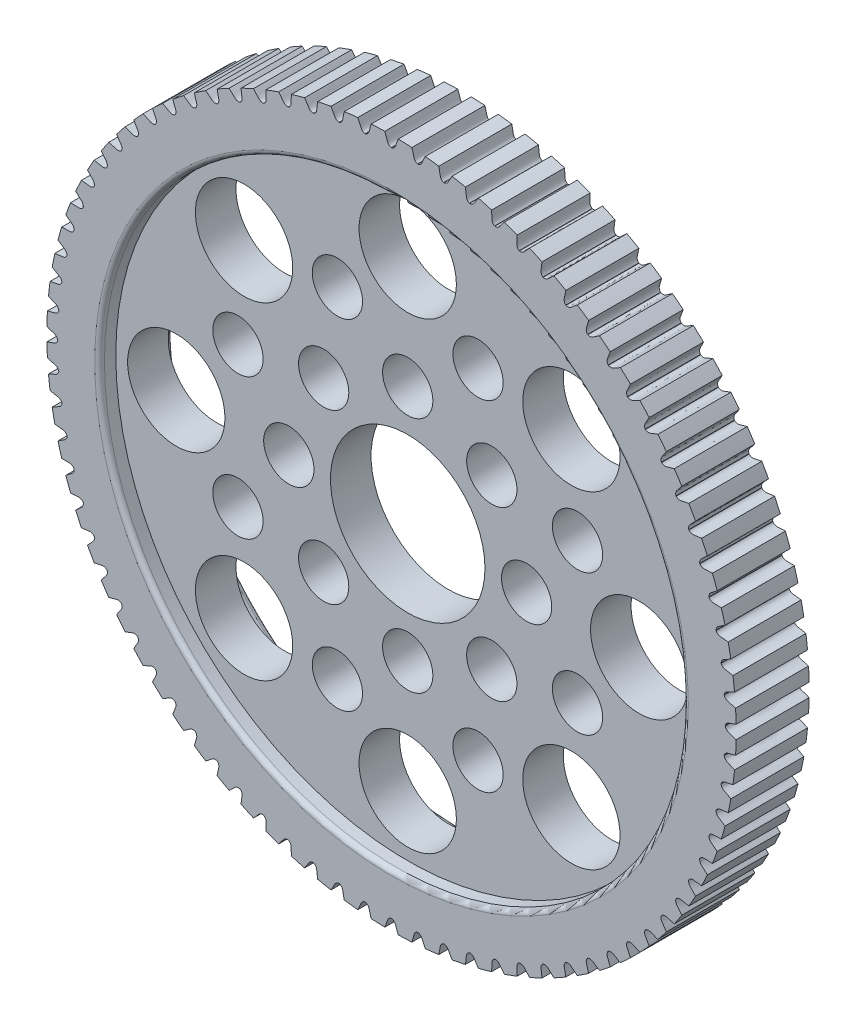
SolidWorks part; units mm, degrees
material "铝合金板 LF5"
ref_plane "前视基准面" through (0, 0, 0) normal (0, 0, 1) x (1, 0, 0)
ref_plane "上视基准面" through (0, 0, 0) normal (0, 1, 0) x (1, 0, 0)
ref_plane "右视基准面" through (0, 0, 0) normal (1, 0, 0) x (0, 0, -1)
sketch "草图1" plane through (0, 0, 0) normal (0, 0, 1) x (1, 0, 0)
  circle A0 centre (0, 0) radius 21.25
  dimension "D1" = 42.5
extrude "凸台-拉伸1" add sketch "草图1" along normal blind 4.5
ref_axis "基准轴1" through (0, 0, 4.5) along (0, 0, -1)
sketch "草图2" plane through (0, 0, 0) normal (0, 0, 1) x (1, 0, 0)
  line L0 (0, 0) -> (0, 21.25) construction
  circle A0 centre (0, 0) radius 21.25 construction
  arc A1 (0.01, 20.5748) -> (-0.01, 20.5748) centre (0, 0) ccw
  arc A2 (2.5283, 24.462) -> (-2.5283, 24.462) centre (0, 0) ccw
  spline S0 degree 3 poles (0.01, 20.5748) (0.2166, 20.6302) (0.2593, 20.8306) (0.3416, 21.0602) (0.3875, 21.1842) (0.439, 21.3141) (0.4959, 21.4499) (0.5585, 21.5914) (0.6271, 21.7385) (0.702, 21.8909) (0.7834, 22.0484) (0.8714, 22.2109) (0.9664, 22.3781) (1.0686, 22.5499) (1.1782, 22.726) (1.2953, 22.9061) (1.4203, 23.0901) (1.5532, 23.2777) (1.6944, 23.4687) (1.8439, 23.6627) (2.002, 23.8596) (2.2277, 24.1293) (2.4055, 24.3293) (2.5283, 24.462) knots 0 0 0 0 0.10185 0.128531 0.156821 0.18672 0.218228 0.251344 0.286069 0.322403 0.360346 0.399897 0.441058 0.483827 0.528205 0.574191 0.621787 0.670991 0.721804 0.774225 0.828256 0.883895 1 1 1 1
  spline S1 degree 3 poles (-0.01, 20.5748) (-0.2166, 20.6302) (-0.2593, 20.8306) (-0.3416, 21.0602) (-0.3875, 21.1842) (-0.439, 21.3141) (-0.4959, 21.4499) (-0.5585, 21.5914) (-0.6271, 21.7385) (-0.702, 21.8909) (-0.7834, 22.0484) (-0.8714, 22.2109) (-0.9664, 22.3781) (-1.0686, 22.5499) (-1.1782, 22.726) (-1.2953, 22.9061) (-1.4203, 23.0901) (-1.5532, 23.2777) (-1.6944, 23.4687) (-1.8439, 23.6627) (-2.002, 23.8596) (-2.2277, 24.1293) (-2.4055, 24.3293) (-2.5283, 24.462) knots 0 0 0 0 0.10185 0.128531 0.156821 0.18672 0.218228 0.251344 0.286069 0.322403 0.360346 0.399897 0.441058 0.483827 0.528205 0.574191 0.621787 0.670991 0.721804 0.774225 0.828256 0.883895 1 1 1 1
extrude "切除-拉伸1" cut sketch "草图2" along normal through all
pattern_circular "阵列(圆周)1" count 80 over 360 about axis through (0, 0, 4.5) along (0, 0, -1) of "切除-拉伸1"
sketch "草图3" plane through (0, 0, 0) normal (0, 0, 1) x (1, 0, 0)
  circle A0 centre (0, 0) radius 20 construction
  dimension "Dn" = 40
sketch "草图4" plane through (0, 0, 0) normal (0, 0, 1) x (1, 0, 0)
  circle A0 centre (0, 0) radius 4.7625
  dimension "D1" = 9.525
extrude "切除-拉伸2" cut sketch "草图4" along normal through all
sketch "草图5" plane through (0, 0, 0) normal (0, 0, 1) x (1, 0, 0)
  line L0 (0, 0) -> (0, 7.33) construction
  line L1 (0, 7.33) -> (0, 14.27) construction
  line L3 (5.1831, 5.1831) -> (4.3358, 10.4676) construction
  line L4 (4.3358, 10.4676) -> (0, 7.33) construction
  circle A0 centre (0, 7.33) radius 1.55
  circle A1 centre (0, 14.27) radius 3
  circle A2 centre (10.0904, 10.0904) radius 3
  circle A3 centre (5.1831, 5.1831) radius 1.55
  circle A4 centre (14.27, 0) radius 3
  circle A5 centre (7.33, 0) radius 1.55
  circle A6 centre (10.0904, -10.0904) radius 3
  circle A7 centre (5.1831, -5.1831) radius 1.55
  circle A8 centre (0, -14.27) radius 3
  circle A9 centre (0, -7.33) radius 1.55
  circle A10 centre (-10.0904, -10.0904) radius 3
  circle A11 centre (-5.1831, -5.1831) radius 1.55
  circle A12 centre (-14.27, 0) radius 3
  circle A13 centre (-7.33, 0) radius 1.55
  circle A14 centre (-10.0904, 10.0904) radius 3
  circle A15 centre (-5.1831, 5.1831) radius 1.55
  circle A16 centre (4.3358, 10.4676) radius 1.55
  circle A17 centre (10.4676, 4.3358) radius 1.55
  circle A18 centre (10.4676, -4.3358) radius 1.55
  circle A19 centre (4.3358, -10.4676) radius 1.55
  circle A20 centre (-4.3358, -10.4676) radius 1.55
  circle A21 centre (-10.4676, -4.3358) radius 1.55
  circle A22 centre (-10.4676, 4.3358) radius 1.55
  circle A23 centre (-4.3358, 10.4676) radius 1.55
  point P6 (0, 0)
  dimension "D3" = 3.1
  dimension "D4" = 6
  dimension "D6" = 3.1
  dimension "D1" = 7.33
  dimension "D2" = 6.94
  dimension "D8" = 7.33
  dimension "D9" = 11.33
  dimension "D5" = 8
  dimension "D7" = 8
extrude "切除-拉伸4" cut sketch "草图5" along normal through all
sketch "草图6" plane through (33.4306, 11.6428, 25.1) normal (0, 0, -1) x (-0.9444, -0.3289, 0)
  circle A0 centre (35.4, 0) radius 18
  dimension "D1" = 36
extrude "切除-拉伸5" cut sketch "草图6" along normal blind 1 from surface starting at face at (-5.78, 0, 4.5)
sketch "草图7" plane through (33.4306, 11.6428, 25.1) normal (0, 0, -1) x (-0.9444, -0.3289, 0)
  circle A0 centre (35.4, 0) radius 18
extrude "切除-拉伸6" cut sketch "草图7" against normal blind 1 from surface starting at face at (-5.78, 0, 0)
fillet "圆角1" radius 0.3 2 edges at (18, 0, 0) (18, 0, 4.5)
sketch "草图8" plane through (0, 0, 0) normal (0, 0, 1) x (1, 0, 0)
  line L0 (0, 0) -> (-19.3748, 0) construction
